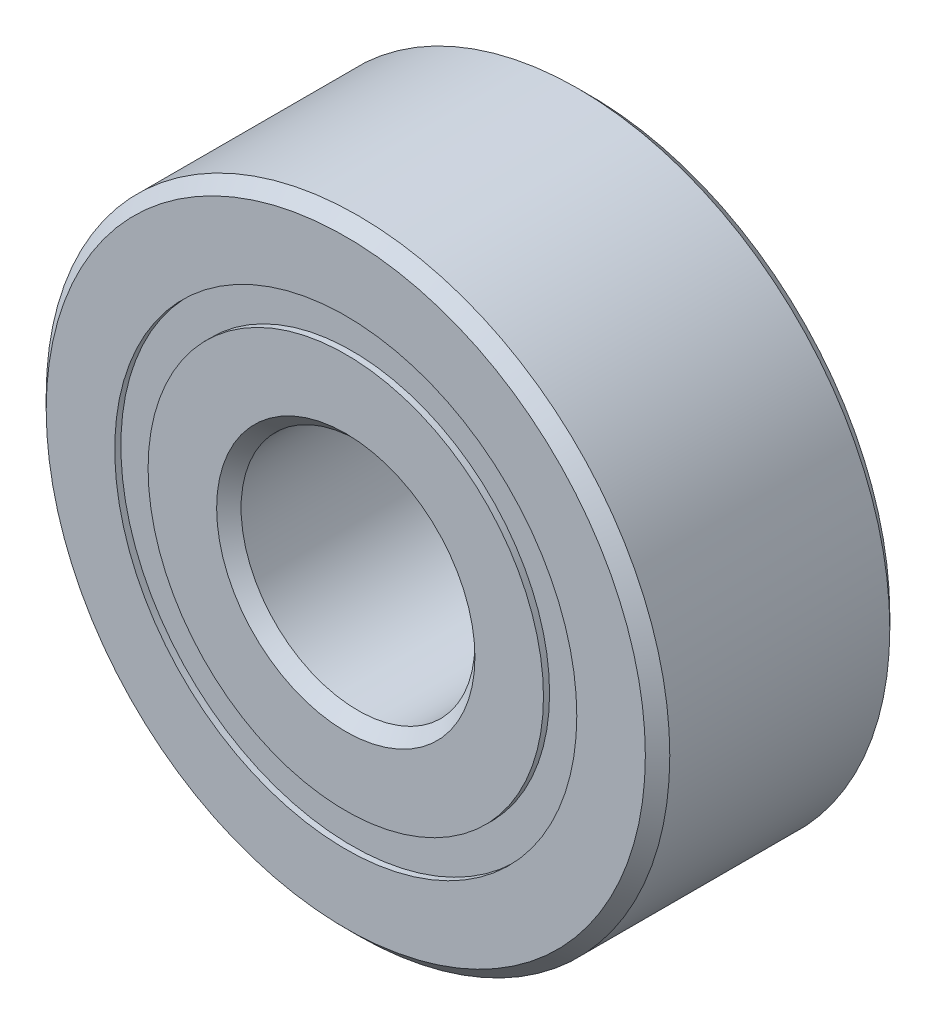
SolidWorks part; units mm, degrees
ref_plane "Front Plane" through (0, 0, 0) normal (0, 0, 1) x (1, 0, 0)
ref_plane "Top Plane" through (0, 0, 0) normal (0, 1, 0) x (1, 0, 0)
ref_plane "Right Plane" through (0, 0, 0) normal (1, 0, 0) x (0, 0, -1)
sketch "Sketch1" plane through (0, 0, 0) normal (1, 0, 0) x (0, 0, -1)
  line L0 (-2.4892, 0) -> (2.4892, 0) construction
  line L1 (0, 6.35) -> (0, -6.35) construction
  line L2 (2.2403, 6.35) -> (-2.2403, 6.35)
  line L3 (-2.2403, 6.35) -> (-2.4892, 6.1011)
  line L4 (-2.4892, 6.1011) -> (-2.4892, 4.705)
  line L5 (-2.4892, 4.705) -> (-1.1063, 4.705)
  line L6 (2.4892, 4.705) -> (1.1063, 4.705)
  line L7 (2.4892, 6.1011) -> (2.4892, 4.705)
  line L8 (2.2403, 6.35) -> (2.4892, 6.1011)
  line L9 (0, 6.35) -> (0, 4.3656) construction
  line L10 (0, 4.3656) -> (0, 2.3812) construction
  arc A0 (-1.1063, 4.705) -> (1.1063, 4.705) centre (0, 4.3656) cw
  point P14 (0, 2.3812)
  dimension "Width" = 4.9784
  dimension "OD" = 12.7
  dimension "D1" = 45
  dimension "D2" = 0.2489
  dimension "Shaft Dia" = 4.7625
  dimension "D3" = 2.2126
  dimension "D4" = 0.3394
revolve "Revolve1" add sketch "Sketch1" angle 360 about L0
sketch "Sketch3" plane through (0, 0, 0) normal (1, 0, 0) x (0, 0, -1)
  line L0 (-2.4892, 4.0262) -> (-1.1063, 4.0262)
  line L1 (0, 6.35) -> (0, -6.35) construction
  line L2 (-2.4892, 6.1011) -> (-2.4892, 4.705) construction
  line L3 (-2.4892, 4.0262) -> (-2.4892, 2.6302)
  line L4 (-2.2403, 6.35) -> (-2.4892, 6.1011) construction
  line L5 (-2.4892, 2.6302) -> (-2.2403, 2.3812)
  line L6 (-2.2403, 2.3812) -> (2.2403, 2.3813)
  line L7 (2.2403, 6.35) -> (2.2403, -6.35) construction
  line L8 (2.2403, 2.3813) -> (2.4892, 2.6302)
  line L9 (2.4892, -6.1011) -> (2.4892, 6.1011) construction
  line L10 (2.4892, 2.6302) -> (2.4892, 4.0262)
  line L11 (2.4892, 4.0262) -> (1.1063, 4.0262)
  line L13 (2.2403, 6.35) -> (2.4892, 6.1011) construction
  arc A0 (1.1063, 4.705) -> (-1.1063, 4.705) centre (0, 4.3656) ccw construction
  arc A1 (1.1063, 4.0262) -> (-1.1063, 4.0262) centre (0, 4.3656) cw
revolve "Revolve3" add sketch "Sketch3" angle 360 about L0
sketch "Sketch4" plane through (0, 0, 0) normal (1, 0, 0) x (0, 0, -1)
  line L0 (-1.1572, 4.3656) -> (1.1572, 4.3656)
  arc A2 (-1.1572, 4.3656) -> (1.1572, 4.3656) centre (0, 4.3656) cw
  arc A3 (1.1063, 4.705) -> (-1.1063, 4.705) centre (0, 4.3656) ccw construction
revolve "Revolve4" add sketch "Sketch4" angle 360 about L0
ref_axis "Axis1" through (0, 0, -2.4892) along (0, 0, 1)
pattern_circular "CirPattern1" count 8 every 45 about axis through (0, 0, -2.4892) along (0, 0, 1) of bodies 104
sketch "Sketch5" plane through (0, 0, 0) normal (1, 0, 0) x (0, 0, -1)
  line L0 (-2.4892, 4.705) -> (-1.1063, 4.705) construction
  line L1 (-2.3647, 4.705) -> (-1.1572, 4.705)
  line L2 (-2.3647, 4.705) -> (-2.3647, 4.0262)
  line L3 (-2.3647, 4.0262) -> (-1.1572, 4.0262)
  line L4 (-1.1572, 4.705) -> (-1.1572, 4.0262)
  line L5 (-2.4892, 4.0262) -> (-1.1063, 4.0262) construction
  line L6 (2.4892, 4.705) -> (1.1063, 4.705) construction
  line L7 (2.3647, 4.705) -> (1.1572, 4.705)
  line L8 (2.3647, 4.705) -> (2.3647, 4.0262)
  line L9 (2.3647, 4.0262) -> (1.1572, 4.0262)
  line L10 (1.1572, 4.705) -> (1.1572, 4.0262)
  line L11 (2.4892, 4.0262) -> (1.1063, 4.0262) construction
  line L12 (-2.2403, 6.35) -> (-2.4892, 6.1011) construction
  point P18 (-2.3647, 6.2255)
revolve "Revolve5" add sketch "Sketch5" angle 360 about L0
equation "\"D2@Sketch1\" = \"Width@Sketch1\"*.05"
equation "\"D3@Sketch1\" = \"Width@Sketch1\"/2.25"
equation "\"D4@Sketch1\" = (((\"OD@Sketch1\"-\"Width@Sketch1\")/2)/3.25)/3.5"
equation "\"D2@CirPattern1\" = 360/\"Balls@CirPattern1\""
